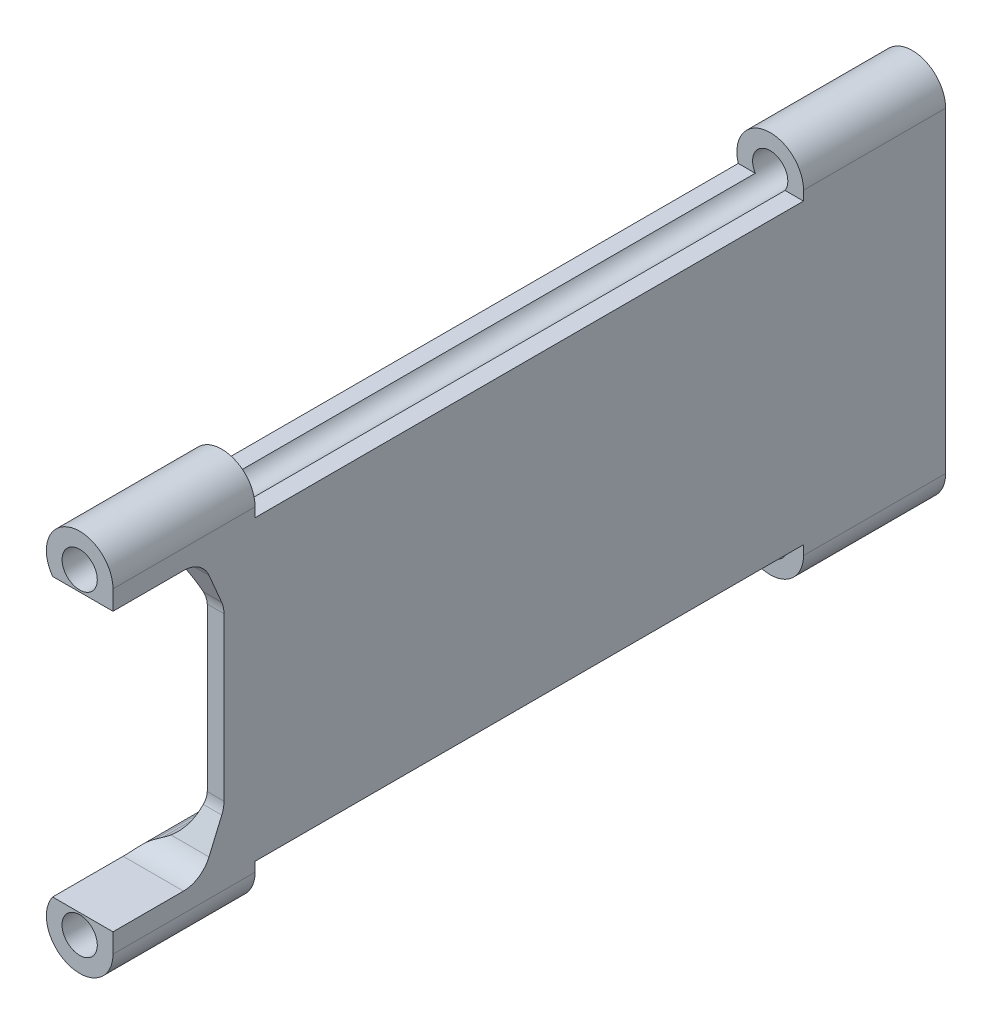
SolidWorks part; units mm, degrees
material "ABS"
ref_plane "Alzado" through (0, 0, 0) normal (0, 0, 1) x (1, 0, 0)
ref_plane "Planta" through (0, 0, 0) normal (0, 1, 0) x (1, 0, 0)
ref_plane "Vista lateral" through (0, 0, 0) normal (1, 0, 0) x (0, 0, -1)
sketch "Croquis1" plane through (0, 0, 0) normal (0, 0, 1) x (1, 0, 0)
  line L5 (-13.465, 0) -> (13.8234, 0) construction
  line L8 (-3, 19.8598) -> (-8.9869, 23.2963)
  line L9 (-3, 19.8598) -> (-3, -19.8598)
  line L10 (0, 28.5) -> (0, -28.5)
  line L11 (-3, -19.8598) -> (-8.9869, -23.2963)
  circle A0 centre (-6, 28.5) radius 3.175
  arc A5 (0, 28.5) -> (-8.9869, 23.2963) centre (-6, 28.5) ccw
  arc A6 (0, -28.5) -> (-8.9869, -23.2963) centre (-6, -28.5) cw
  circle A7 centre (-6, -28.5) radius 3.175
  point P7 (0, 0)
  point P15 (0, 0)
  point P16 (-3, 0)
  point P17 (-3, 0)
  dimension "D1" = 6.35
  dimension "D2" = 57
  dimension "D3" = 3
  dimension "D4" = 6
extrude "Saliente-Extruir1" add sketch "Croquis1" against normal blind 150
fillet "Redondeo1" radius 10 2 edges at (-3, -19.8598, -75) (-3, 19.8598, -75)
sketch "Croquis2" plane through (0, 0, 0) normal (1, 0, 0) x (0, 0, -1)
  line L0 (16, 25) -> (20, 15.6468)
  line L1 (20, 15.6468) -> (20, -15.6468)
  line L2 (-29.8735, 0) -> (35.3957, 0) construction
  line L3 (16, 25) -> (-29.8735, 25)
  line L4 (-29.8735, 25) -> (-29.8735, -25)
  line L5 (16, -25) -> (-29.8735, -25)
  line L6 (16, -25) -> (20, -15.6468)
  line L8 (0, -28.5) -> (0, 28.5) construction
  point P2 (21.1355, 15.6468)
  point P10 (20, 0)
  point P12 (12.0997, -25)
  point P13 (140, -18.1651)
  dimension "D1" = 50
  dimension "D2" = 16
  dimension "D3" = 20
extrude "Cortar-Extruir1" cut sketch "Croquis2" against normal through all
fillet "Redondeo2" radius 5 4 edges at (-1.5626, 15.6468, -20) (-1.5626, -15.6468, -20) (-5.4367, -25, -16) (-5.4367, 25, -16)
sketch "Croquis3" plane through (0, 0, 0) normal (1, 0, 0) x (0, 0, -1)
  line L0 (0, 0) -> (150, 0) construction
  line L1 (25.6041, 44.9478) -> (124.3959, 44.9478)
  line L2 (25.6041, 44.9478) -> (25.6041, 26.8024)
  line L3 (25.6041, 26.8024) -> (124.3959, 26.8024)
  line L4 (124.3959, 44.9478) -> (124.3959, 26.8024)
  line L5 (124.3959, -44.9478) -> (124.3959, -26.8024)
  line L6 (25.6041, -26.8024) -> (124.3959, -26.8024)
  line L7 (25.6041, -44.9478) -> (25.6041, -26.8024)
  line L8 (25.6041, -44.9478) -> (124.3959, -44.9478)
  line L9 (150, 14.0695) -> (150, -14.0695) construction
  point P11 (0, 0)
  point P12 (150.4612, 0)
  point P13 (150, 0)
  point P16 (75, 0)
  point P17 (75, -26.8024)
extrude "Cortar-Extruir2" cut sketch "Croquis3" against normal through all
